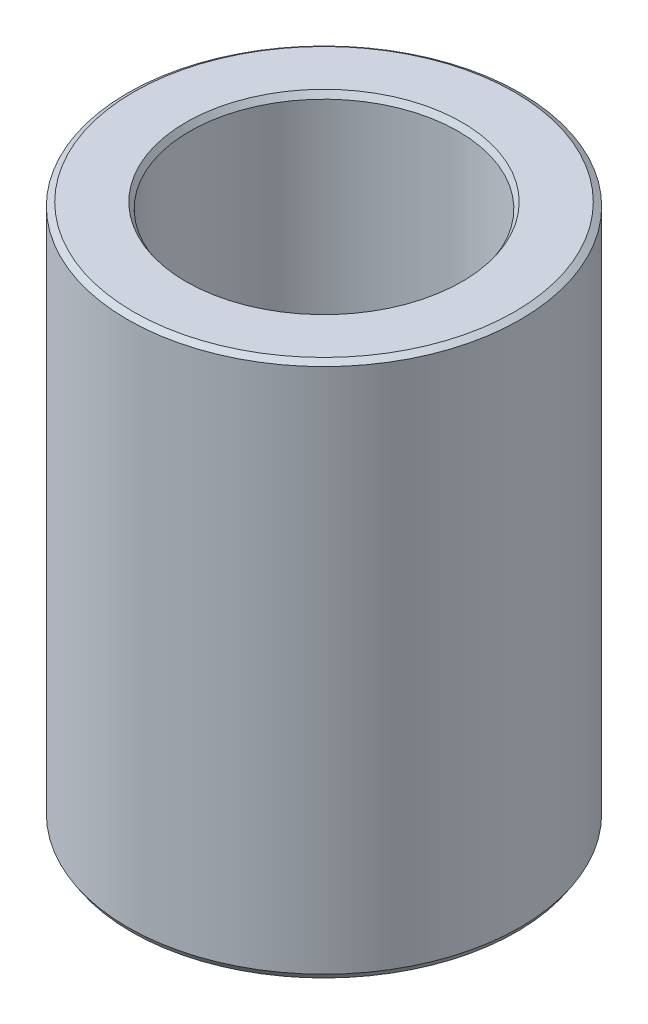
SolidWorks part; units mm, degrees
ref_plane "Front Plane" through (0, 0, 0) normal (0, 0, 1) x (1, 0, 0)
ref_plane "Top Plane" through (0, 0, 0) normal (0, 1, 0) x (1, 0, 0)
ref_plane "Right Plane" through (0, 0, 0) normal (1, 0, 0) x (0, 0, -1)
sketch "Sketch1" plane through (0, 0, 0) normal (0, 1, 0) x (1, 0, 0)
  circle A0 centre (0, 0) radius 22.5
  dimension "SLEEVE_OD" = 45
extrude "Boss-Extrude1" add sketch "Sketch1" along normal blind 61.413
sketch "Sketch2" plane through (0, 0, 0) normal (0, 1, 0) x (1, 0, 0)
  circle A0 centre (0, 0) radius 15.387
  dimension "BORE_D" = 30.774
extrude "Cut-Extrude1" cut sketch "Sketch2" along normal through all
chamfer "Chamfer1" distance 0.4313 angle 57.53 4 edges at (0, 61.413, 15.387) (0, 0, 15.387) (0, 0, 22.5) (0, 61.413, 22.5) first distance on face at (0, 61.413, 15.387) first distance on face at (0, 0, 15.387) first distance on face at (0, 61.413, 22.5)
